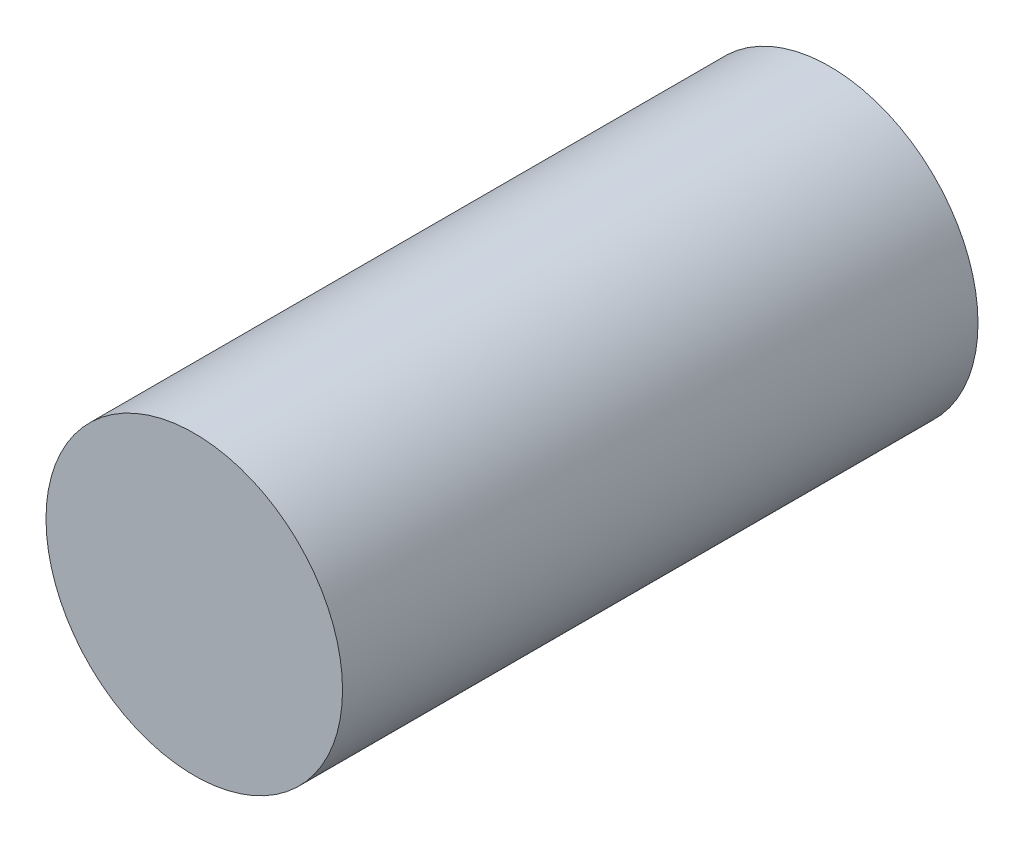
SolidWorks part; units mm, degrees
ref_plane "前视基准面" through (0, 0, 0) normal (0, 0, 1) x (1, 0, 0)
ref_plane "上视基准面" through (0, 0, 0) normal (0, 1, 0) x (1, 0, 0)
ref_plane "右视基准面" through (0, 0, 0) normal (1, 0, 0) x (0, 0, -1)
sketch "Sketch1" plane through (0, 0, 0) normal (0, 0, 1) x (1, 0, 0)
  circle A0 centre (0, 0) radius 3.5
  dimension "D1" = 7
extrude "Boss-Extrude1" add sketch "Sketch1" along normal blind 15
